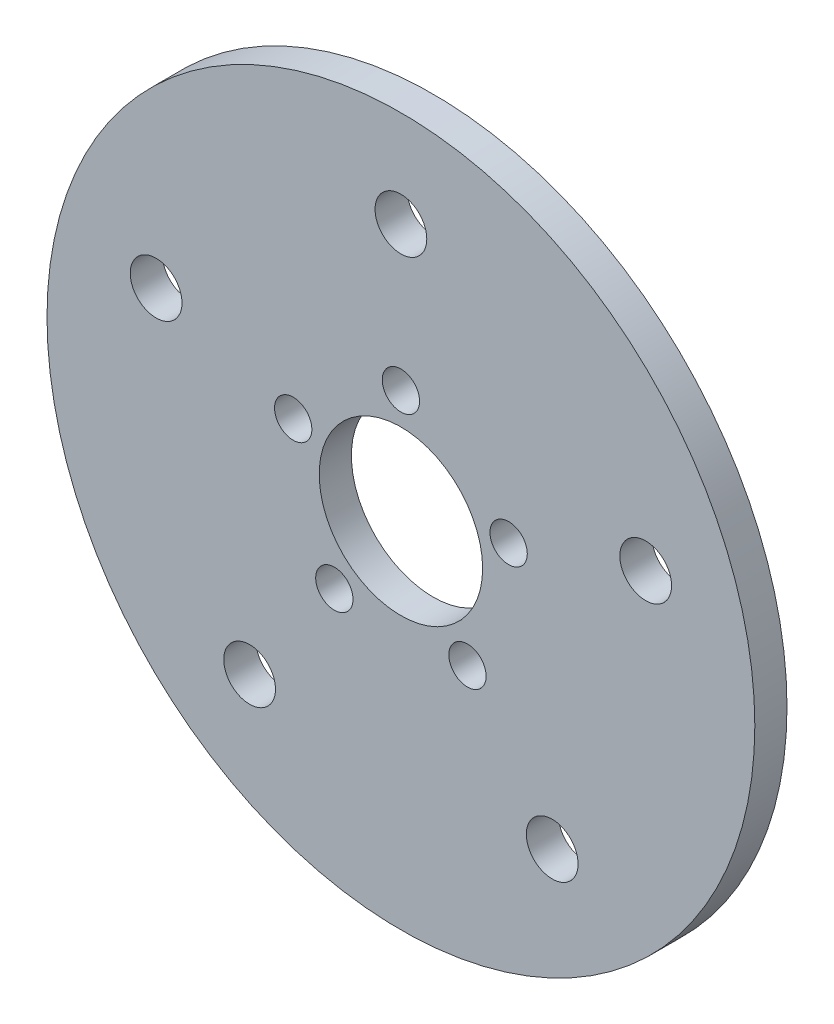
SolidWorks part; units mm, degrees
ref_plane "Front Plane" through (0, 0, 0) normal (0, 0, 1) x (1, 0, 0)
ref_plane "Top Plane" through (0, 0, 0) normal (0, 1, 0) x (1, 0, 0)
ref_plane "Right Plane" through (0, 0, 0) normal (1, 0, 0) x (0, 0, -1)
sketch "Sketch1" plane through (0, 0, 0) normal (0, 0, 1) x (1, 0, 0)
  line L0 (0, 0) -> (0, 11.176) construction
  line L1 (0, 25.4) -> (0, 0) construction
  circle A0 centre (0, 0) radius 34.925
  circle A1 centre (0, 0) radius 8.0645
  circle A2 centre (0, 11.176) radius 1.8415
  circle A3 centre (0, 25.4) radius 2.5527
  circle A4 centre (10.629, 3.4536) radius 1.8415
  circle A5 centre (24.1568, 7.849) radius 2.5527
  circle A6 centre (6.5691, -9.0416) radius 1.8415
  circle A7 centre (14.9297, -20.549) radius 2.5527
  circle A8 centre (-6.5691, -9.0416) radius 1.8415
  circle A9 centre (-14.9297, -20.549) radius 2.5527
  circle A10 centre (-10.629, 3.4536) radius 1.8415
  circle A11 centre (-24.1568, 7.849) radius 2.5527
  point P9 (0, 0)
  dimension "D1" = 69.85
  dimension "D2" = 16.129
  dimension "D4" = 3.683
  dimension "D5" = 5.1054
  dimension "D3" = 11.176
  dimension "D6" = 25.4
  dimension "D7" = 5
extrude "Boss-Extrude1" add sketch "Sketch1" along normal blind 3.175
